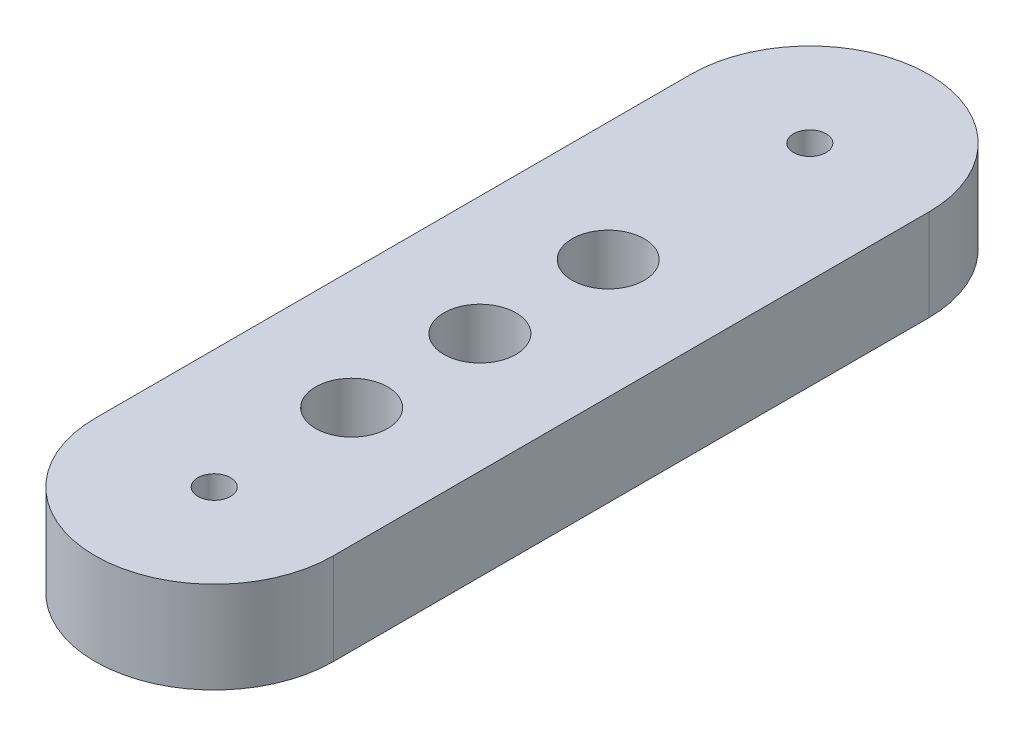
SolidWorks part; units mm, degrees
ref_plane "Front Plane" through (0, 0, 0) normal (0, 0, 1) x (1, 0, 0)
ref_plane "Top Plane" through (0, 0, 0) normal (0, 1, 0) x (1, 0, 0)
ref_plane "Right Plane" through (0, 0, 0) normal (1, 0, 0) x (0, 0, -1)
sketch "Sketch1" plane through (0, 0, 0) normal (0, 1, 0) x (1, 0, 0)
  line L0 (0, -20.6375) -> (0, 20.6375) construction
  line L1 (-8.255, -20.6375) -> (-8.255, 20.6375)
  line L2 (8.255, -20.6375) -> (8.255, 20.6375)
  arc A0 (-8.255, -20.6375) -> (8.255, -20.6375) centre (0, -20.6375) ccw
  arc A1 (8.255, 20.6375) -> (-8.255, 20.6375) centre (0, 20.6375) ccw
  circle A2 centre (0, 20.6375) radius 1.1303
  circle A3 centre (0, -20.6375) radius 1.1303
  circle A4 centre (0, -11.1125) radius 2.5
  circle A5 centre (0, -2.2225) radius 2.5
  circle A6 centre (0, 6.6675) radius 2.5
  point P2 (0, 0)
  dimension "D3" = 2.2606
  dimension "D4" = 5
  dimension "D1" = 16.51
  dimension "D2" = 8.89
  dimension "D5" = 9.525
  dimension "D6" = 13.97
  dimension "D7" = 8.89
extrude "Boss-Extrude1" add sketch "Sketch1" along normal blind 6.35
